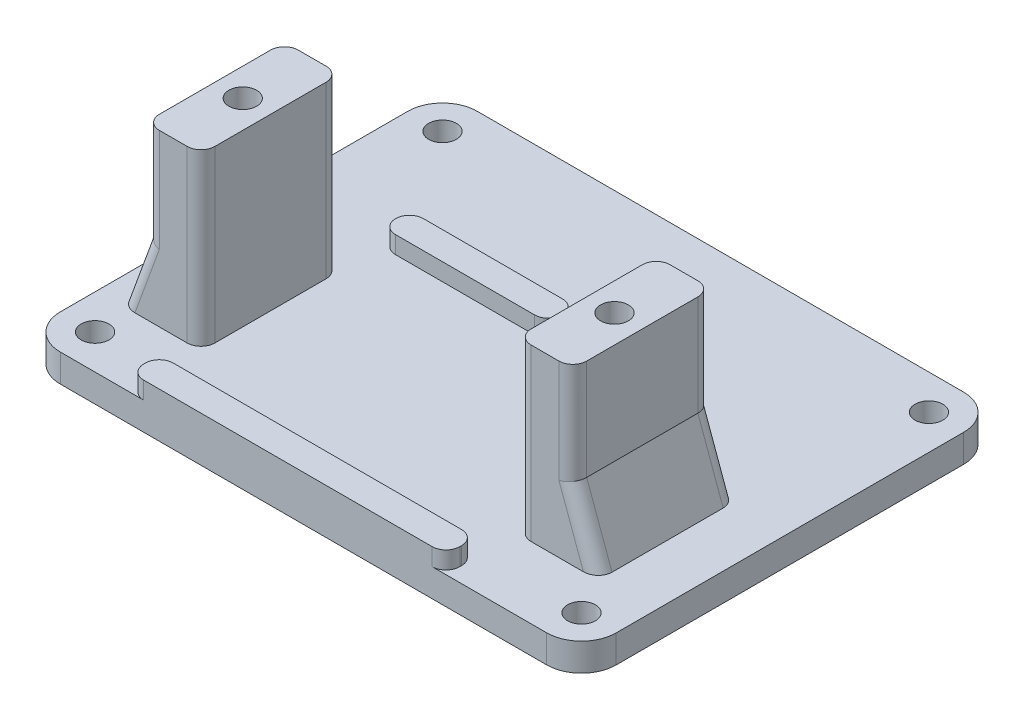
SolidWorks part; units mm, degrees
note: The reader was unsure of these and kept them because the rebuilt part matched: shared geometry of "Эскиз2<3>".
ref_plane "Спереди" through (0, 0, 0) normal (0, 0, 1) x (1, 0, 0)
ref_plane "Сверху" through (0, 0, 0) normal (0, 1, 0) x (1, 0, 0)
ref_plane "Справа" through (0, 0, 0) normal (1, 0, 0) x (0, 0, -1)
sketch "Эскиз1" plane through (0, 0, 0) normal (0, 1, 0) x (1, 0, 0)
  line L1 (-40, -30) -> (40, -30)
  line L2 (-40, -30) -> (-40, 30)
  line L3 (-40, 30) -> (40, 30)
  line L4 (40, -30) -> (40, 30)
  line L5 (0, 30) -> (0, -30) construction
  line L6 (-40, 0) -> (40, 0) construction
  line L7 (-35, -25) -> (35, -25) construction
  line L8 (-35, -25) -> (-35, 25) construction
  line L9 (-35, 25) -> (35, 25) construction
  line L10 (35, -25) -> (35, 25) construction
  line L11 (0, 25) -> (0, -25) construction
  line L12 (-35, 0) -> (35, 0) construction
  circle A0 centre (-35, 25) radius 2
  circle A1 centre (35, 25) radius 2
  circle A2 centre (-35, -25) radius 2
  circle A3 centre (35, -25) radius 2
  point P0 (0, 0)
  point P6 (-35, 24.4229)
  point P7 (0, 0)
  point P12 (35.4724, 25)
  point P14 (-35, -24.5212)
  point P16 (34.5635, -25)
  dimension "D3" = 4
  dimension "D4" = 70
  dimension "D1" = 80
  dimension "D2" = 60
  dimension "D5" = 50
extrude "Бобышка-Вытянуть1" add sketch "Эскиз1" along normal blind 4
fillet "Скругление1" radius 5 4 edges at (-40, 2, -30) (40, 2, -30) (40, 2, 30) (-40, 2, 30)
sketch "Эскиз2" plane through (0, 4, 0) normal (0, 1, 0) x (1, 0, 0)
  line L0 (-25, 6.25) -> (-1, 6.25)
  line L1 (-25, -25.75) -> (20.5, -25.75) construction
  line L2 (-25, -25.75) -> (-25, 6.25) construction
  line L3 (-25, 6.25) -> (20.5, 6.25) construction
  line L4 (20.5, -25.75) -> (20.5, 6.25) construction
  line L5 (-2.25, 0.6) -> (-2.25, -19.0179) construction
  line L6 (-25, -9.75) -> (20.5, -9.75) construction
  line L7 (-1, 6.25) -> (-1, 10.25)
  line L8 (-1, 10.25) -> (-25, 10.25)
  line L14 (20.5, -9.75) -> (20.5, 0.25)
  line L15 (20.5, 0.25) -> (28.5, 0.25)
  line L16 (28.5, 0.25) -> (28.5, -19.75)
  line L17 (28.5, -19.75) -> (20.5, -19.75)
  line L18 (20.5, -19.75) -> (20.5, -9.75)
  line L19 (-25, 10.25) -> (-25, 6.25)
  line L23 (-25, -19.75) -> (-25, -9.75)
  line L24 (-33, -19.75) -> (-25, -19.75)
  line L25 (-33, 0.25) -> (-33, -19.75)
  line L26 (-25, 0.25) -> (-33, 0.25)
  line L27 (-25, -9.75) -> (-25, 0.25)
  line L28 (-35, -30) -> (35, -30) construction
  line L29 (-25, -25.75) -> (20.5, -25.75)
  line L30 (-40, 25) -> (-40, -25) construction
  line L31 (35, 25) -> (12, 25) construction
  line L32 (35, 25) -> (35, 7) construction
  line L33 (35, 7) -> (12, 7) construction
  line L34 (12, 25) -> (12, 7) construction
  line L35 (20.5, 0.25) -> (11.5, 0.25) construction
  line L36 (20.5, 0.25) -> (20.5, 8.75) construction
  line L37 (20.5, 8.75) -> (11.5, 8.75) construction
  line L38 (11.5, 0.25) -> (11.5, 8.75) construction
  line L40 (-25, -25.75) -> (-25, -30)
  line L41 (-25, -30) -> (20.5, -30)
  line L42 (20.5, -25.75) -> (20.5, -30)
  point P0 (-2.25, -9.75)
  dimension "D1" = 45.5
  dimension "D2" = 32
  dimension "D3" = 4
  dimension "D4" = 24
  dimension "D5" = 20
  dimension "D6" = 8
  dimension "D8" = 7
  dimension "D10" = 23
  dimension "D11" = 18
  dimension "D12" = 9
extrude "Бобышка-Вытянуть2" add sketch "Эскиз2" along normal blind 2.5
extrude "Бобышка-Вытянуть3" add sketch "Эскиз2<3>" along normal blind 24.5 contours L18 L17 L16 L15 L14 | L23 L27 L26 L25 L24
sketch "Эскиз2<3>" plane through (0, 4, 0) normal (0, 1, 0) x (1, 0, 0) same geometry as "Эскиз2"
sketch "Эскиз3" plane through (0, 28.5, 0) normal (0, 1, 0) x (1, 0, 0)
  line L0 (-29, 0.25) -> (-29, -9.75) construction
  line L1 (-25, 0.25) -> (-33, 0.25) construction
  line L2 (-29, -9.75) -> (24.5, -9.75) construction
  line L3 (24.5, -9.75) -> (24.5, 14.2462) construction
  line L4 (20.5, 0.25) -> (28.5, 0.25) construction
  line L5 (20.5, -19.75) -> (20.5, 0.25) construction
  circle A1 centre (-29, -9.75) radius 2
  circle A2 centre (24.5, -9.75) radius 2
  point P10 (-0.3912, -4.8174)
  point P11 (24.5, 0.25)
  point P14 (20.5, -9.75)
  dimension "D1" = 4
extrude "Вырез-Вытянуть1" cut sketch "Эскиз3" against normal blind 7
chamfer "Фаска1" distance 10 angle 20 2 edges at (28.5, 4, 9.75) (-33, 4, 9.75) first distance on face at (28.5, 16.25, 9.75) first distance on face at (-33, 16.25, 9.75)
fillet "Скругление2" radius 2 8 edges at (30.3199, 9, -0.25) (20.5, 16.25, -0.25) (30.3199, 9, 19.75) (20.5, 16.25, 19.75) (-34.8199, 9, -0.25) (-34.8199, 9, 19.75) (-25, 16.25, -0.25) (-25, 16.25, 19.75)
fillet "Скругление3" radius 2 8 edges at (-25, 5.25, -6.25) (-1, 5.25, -10.25) (-25, 5.25, -10.25) (-1, 5.25, -6.25) (20.5, 5.25, 25.75) (20.5, 5.25, 30) (-25, 5.25, 30) (-25, 5.25, 25.75)
fillet "Скругление4" radius 2 4 edges at (28.5, 18.3262, -0.25) (28.5, 18.3262, 19.75) (-33, 18.3262, -0.25) (-33, 18.3262, 19.75)
